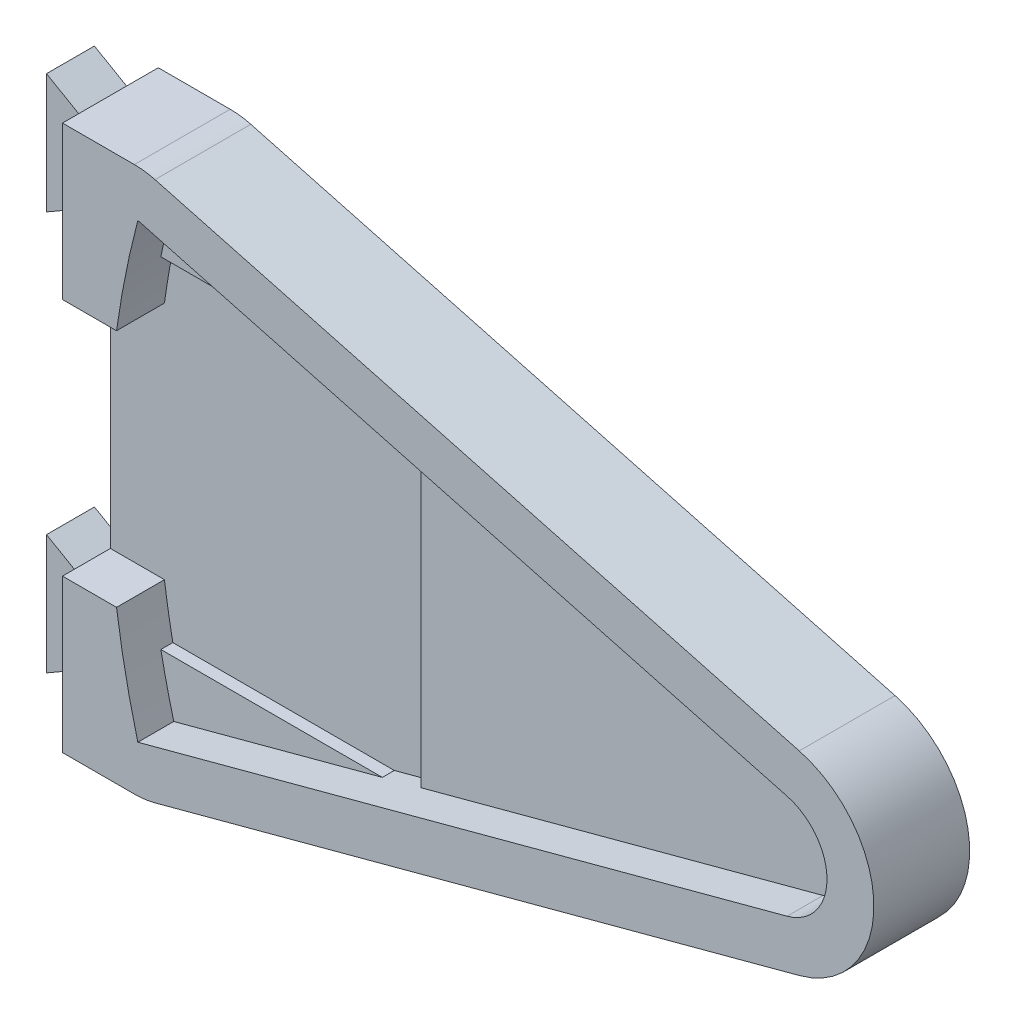
SolidWorks part; units mm, degrees
ref_plane "Front Plane" through (0, 0, 0) normal (0, 0, 1) x (1, 0, 0)
ref_plane "Top Plane" through (0, 0, 0) normal (0, 1, 0) x (1, 0, 0)
ref_plane "Right Plane" through (0, 0, 0) normal (1, 0, 0) x (0, 0, -1)
sketch "Sketch1" plane through (0, 0, 0) normal (0, 0, 1) x (1, 0, 0)
  line L0 (-4.8058, 6.263) -> (-85.8802, 27.9868) construction
  line L1 (-85.8802, -27.9868) -> (-4.8058, -6.263) construction
  line L2 (-89.5, 0) -> (0, 0) construction
  line L3 (-85.9704, -28.1425) -> (-4.7729, -6.3857) construction
  line L4 (-4.7729, 6.3857) -> (-85.9704, 28.1425) construction
  line L5 (-83.9089, -33.8018) -> (-3.22, -12.1813)
  line L6 (-3.22, 12.1813) -> (-83.9089, 33.8018)
  line L7 (-95.5, 34.1425) -> (-95.5, -34.1425)
  line L8 (-89.5, 0) -> (-95.5, 0) construction
  line L9 (-84.4175, -33.9381) -> (-3.22, -12.1813) construction
  line L10 (-3.22, 12.1813) -> (-84.4175, 33.9381) construction
  line L11 (-95.5, 34.1425) -> (-86.4971, 34.1425)
  line L12 (-95.5, -34.1425) -> (-86.4971, -34.1425)
  line L13 (-86.0606, -28.2981) -> (-4.7401, -6.5084)
  line L14 (-4.7401, 6.5084) -> (-86.0606, 28.2981)
  arc A0 (-85.8802, 27.9868) -> (-85.8802, -27.9868) centre (20.5, 0) ccw construction
  arc A1 (-4.8058, -6.263) -> (-4.8058, 6.263) centre (-6.484, 0) ccw construction
  arc A2 (-85.9704, 28.1425) -> (-85.9704, -28.1425) centre (20.5, 0) ccw construction
  arc A3 (-4.7729, -6.3857) -> (-4.7729, 6.3857) centre (-6.484, 0) ccw construction
  arc A4 (-3.22, -12.1813) -> (-3.22, 12.1813) centre (-6.484, 0) ccw
  arc A5 (-86.4971, 34.1425) -> (-83.9089, 33.8018) centre (-86.4971, 24.1425) cw
  arc A6 (-86.4971, -34.1425) -> (-83.9089, -33.8018) centre (-86.4971, -24.1425) ccw
  arc A7 (-86.0606, 28.2981) -> (-86.0606, -28.2981) centre (20.5, 0) ccw
  arc A8 (-4.7401, -6.5084) -> (-4.7401, 6.5084) centre (-6.484, 0) ccw
  point P6 (0, 0)
  point P23 (-95.5, 0)
  dimension "D1" = 110
  dimension "D2" = 6.484
  dimension "D12" = 10
  dimension "D14" = 10
  dimension "D3" = 81.0744
  dimension "D4" = 81.0744
  dimension "D5" = 21.7238
  dimension "D6" = 21.7238
  dimension "D7" = 55.9737
  dimension "D10" = 6
  dimension "D11" = 6
  dimension "D13" = 6
  dimension "D8" = 0.127
  dimension "D9" = 6
  dimension "D15" = 0.127
extrude "Boss-Extrude1" add sketch "Sketch1" along normal blind 6 contours L3 A3 L4 A2 | L12 A6 L5 A4 L6 A5 L11 L7 A3 L3 A2 L4 | L13 A8 L14 A7 region at (-85.3516, -32.8431, 0) region at (-54.6283, 0, 0)
extrude "Boss-Extrude2" add sketch "Sketch1<3>" along normal blind 6 from surface starting at face at (-66.1103, 0, 6)
sketch "Sketch1<3>" plane through (0, 0, 0) normal (0, 0, 1) x (1, 0, 0) same geometry as "Sketch1"
sketch "Sketch2" plane through (0, 0, 0) normal (0, 0, 1) x (1, 0, 0)
  line L4 (0, 0) -> (-95.5, 0) construction
  line L6 (-95.5, -34.1425) -> (-95.5, 34.1425) construction
  line L7 (-95.5, 27.8812) -> (-103.5, 32.5)
  line L8 (-103.5, 32.5) -> (-103.5, 17.5)
  line L9 (-103.5, 17.5) -> (-95.5, 22.1188)
  line L10 (-103.5, -17.5) -> (-95.5, -22.1188)
  line L11 (-103.5, -32.5) -> (-103.5, -17.5)
  line L12 (-95.5, -27.8812) -> (-103.5, -32.5)
  line L13 (-95.5, 27.8812) -> (-95.5, 22.1188)
  line L14 (-95.5, -22.1188) -> (-95.5, -27.8812)
  point P4 (-103.5, 25)
  dimension "D1" = 25
  dimension "D2" = 60
  dimension "D3" = 60
  dimension "D4" = 15
  dimension "D5" = 8
extrude "Boss-Extrude3" add sketch "Sketch2" along normal blind 6
sketch "Sketch3" plane through (-95.5, 0, 0) normal (-1, 0, 0) x (0, 0, 1)
  line L0 (12, -34.1425) -> (12, 34.1425) construction
  line L1 (12, 15) -> (6, 15)
  line L2 (12, 15) -> (12, -15)
  line L3 (12, -15) -> (6, -15)
  line L4 (6, 15) -> (6, -15)
  line L6 (0, 0) -> (50000, 0) construction
  line L8 (6, 32.5) -> (6, 17.5) construction
  point P13 (6, 0)
  dimension "D1" = 15
extrude "Cut-Extrude1" cut sketch "Sketch3" against normal blind 10
sketch "Sketch4" plane through (0, 0, 6) normal (0, 0, 1) x (1, 0, 0)
  line L0 (0.127, 0) -> (-49999.873, 0) construction
  line L1 (-85.0915, 20) -> (-55.0915, 20) construction
  line L2 (-85.0915, 20) -> (-85.0915, -20) construction
  line L3 (-85.0915, -20) -> (-55.0915, -20) construction
  line L4 (-55.0915, 20) -> (-55.0915, -20) construction
  line L6 (-55.0915, 20) -> (-55.0915, -20)
  line L13 (-86.0606, 28.2981) -> (-4.7401, 6.5084) construction
  line L14 (-86.0606, 28.2981) -> (-59.9362, 21.2981)
  line L15 (-87.6773, 21.2981) -> (-59.9362, 21.2981)
  line L16 (-87.6773, -21.2981) -> (-59.9362, -21.2981)
  line L17 (-86.0606, -28.2981) -> (-59.9362, -21.2981)
  line L18 (-55.0915, 20) -> (-4.7401, 6.5084)
  line L19 (-55.0915, -20) -> (-4.7401, -6.5084)
  arc A2 (-4.7401, -6.5084) -> (-4.7401, 6.5084) centre (-6.484, 0) ccw construction
  arc A5 (-86.0606, 28.2981) -> (-88.7289, 15) centre (20.5, 0) ccw construction
  arc A6 (-86.0606, 28.2981) -> (-87.6773, 21.2981) centre (20.5, 0) ccw
  arc A7 (-4.7401, -6.5084) -> (-4.7401, 6.5084) centre (-6.484, 0) ccw
  arc A8 (-86.0606, -28.2981) -> (-87.6773, -21.2981) centre (20.5, 0) cw
  point P9 (-55.0915, 0)
  dimension "D1" = 30
  dimension "D2" = 40
  dimension "D3" = 7
  dimension "D4" = 20
extrude "Boss-Extrude4" add sketch "Sketch4" along normal blind 1.5
